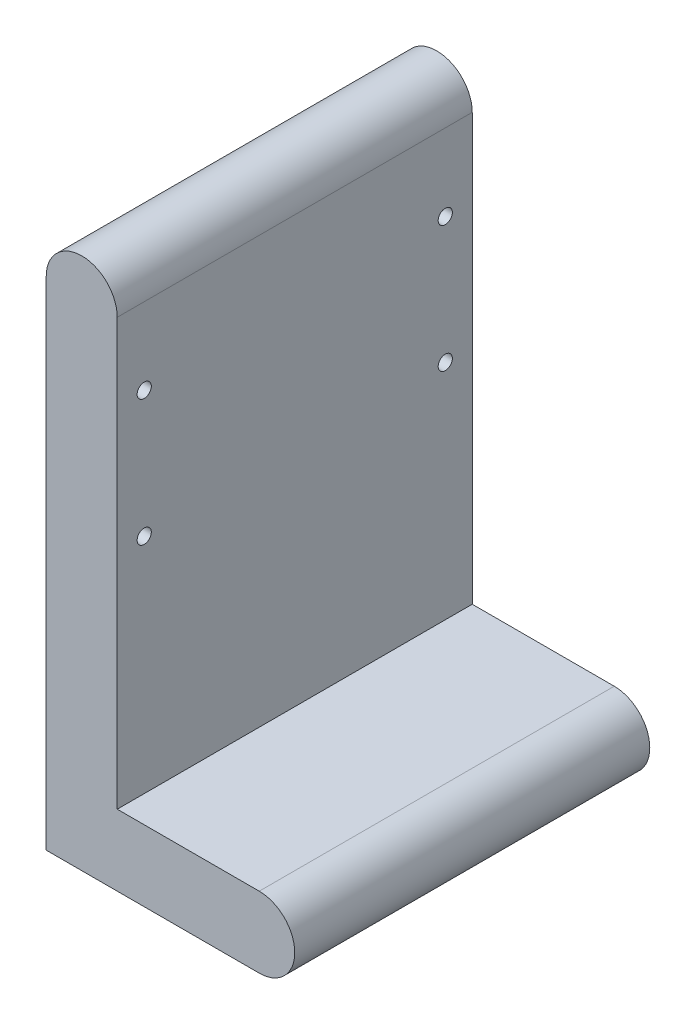
SolidWorks part; units mm, degrees
ref_plane "Front Plane" through (0, 0, 0) normal (0, 0, 1) x (1, 0, 0)
ref_plane "Top Plane" through (0, 0, 0) normal (0, 1, 0) x (1, 0, 0)
ref_plane "Right Plane" through (0, 0, 0) normal (1, 0, 0) x (0, 0, -1)
sketch "Sketch1" plane through (0, 0, 0) normal (0, 0, 1) x (1, 0, 0)
  line L0 (0, 60) -> (0, 0)
  line L1 (0, 0) -> (20, 0)
  line L2 (-10, 60) -> (-10, -10)
  line L3 (-10, -10) -> (20, -10)
  arc A0 (0, 60) -> (-10, 60) centre (-5, 60) ccw
  arc A1 (20, 0) -> (20, -10) centre (20, -5) cw
  dimension "D1" = 60
  dimension "D2" = 20
  dimension "D3" = 10
extrude "Boss-Extrude1" add sketch "Sketch1" along normal blind 50
sketch "Sketch2" plane through (-10, 0, 0) normal (-1, 0, 0) x (0, 0, 1)
  line L0 (25, -10) -> (25, 65)
  line L1 (50, -10) -> (0, -10) construction
  line L2 (50, 65) -> (0, 65) construction
  line L3 (0, 30) -> (50, 30)
  line L4 (0, 60) -> (0, -10) construction
  line L5 (50, 60) -> (50, -10) construction
  circle A0 centre (3.8, 31.4) radius 1
  circle A2 centre (3.8, 49.2) radius 1
  circle A5 centre (46.2, 31.4) radius 1
  circle A6 centre (46.2, 49.2) radius 1
  dimension "D4" = 2
  dimension "D1" = 40
  dimension "D2" = 1.4
  dimension "D3" = 21.2
  dimension "D6" = 17.8
  dimension "D5" = 2
extrude "Cut-Extrude1" cut sketch "Sketch2" against normal blind 10 contours A5 | A2 | A0 | A6 region at (-10, 31.4, 3.8) region at (-10, 49.2, 3.8) region at (-10, 31.4, 46.2)
equation "\"1ز4\"=0.346319"
